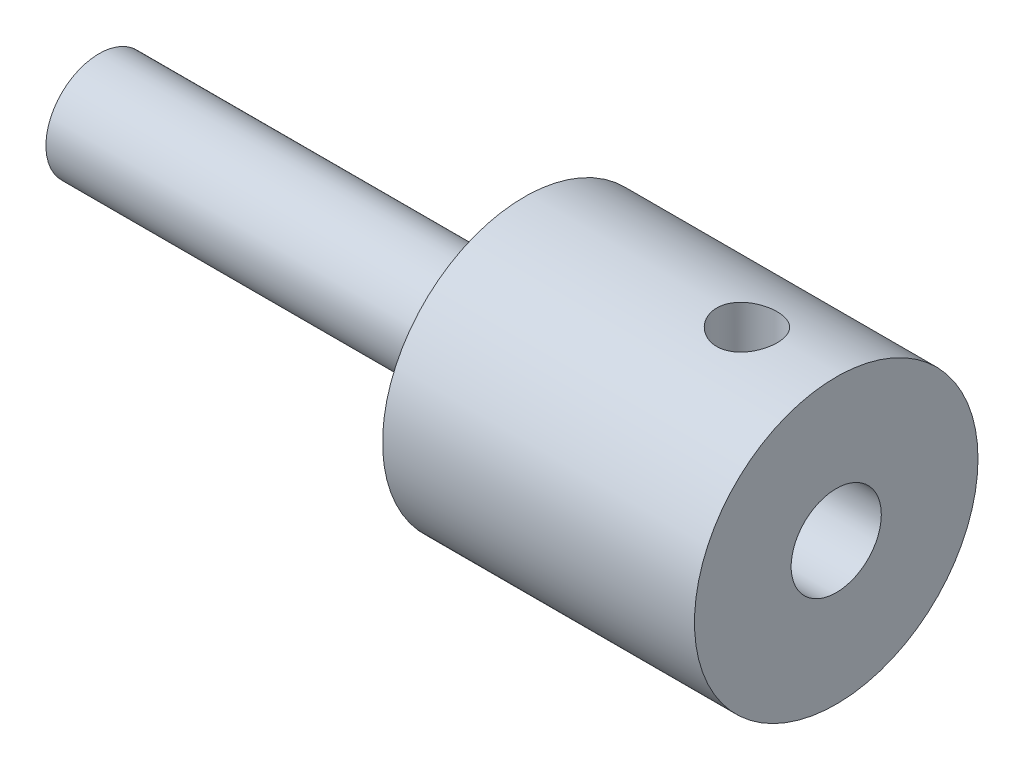
SolidWorks part; units mm, degrees
material "Plain Carbon Steel"
ref_plane "Front Plane" through (0, 0, 0) normal (0, 0, 1) x (1, 0, 0)
ref_plane "Top Plane" through (0, 0, 0) normal (0, 1, 0) x (1, 0, 0)
ref_plane "Right Plane" through (0, 0, 0) normal (1, 0, 0) x (0, 0, -1)
sketch "Sketch1" plane through (0, 0, 0) normal (1, 0, 0) x (0, 0, -1)
  circle A0 centre (0, 0) radius 6.35
  dimension "D1" = 12.7
extrude "Boss-Extrude1" add sketch "Sketch1" along normal blind 33.02
hole_wizard "#21 (0.159) Diameter Hole1" positions "Sketch4" profile "Sketch3" hole size "#21" standard "ANSI Inch"
sketch "Sketch4" plane through (33.02, 0, 0) normal (1, 0, 0) x (0, 0, -1)
  point P0 (0, 0)
sketch "Sketch3" plane through (33.02, 0, 0) normal (0, 1, 0) x (0, 0, -1)
  line L0 (0, 0) -> (0, 9.2133)
  line L1 (0, 9.2133) -> (2.0193, 8)
  line L2 (2.0193, 8) -> (2.0193, 0)
  line L5 (2.0193, 0) -> (0, 0)
  line L10 (0, 9.2133) -> (-2.0193, 8) construction
  line L11 (0, -6.35) -> (0, 107.95) construction
  dimension "Hole Dia." = 4.0386
  dimension "Hole Depth" = 8
  dimension "Drill Angle" = 118
hole_wizard "#6-32 Tapped Hole1" positions "Sketch6" profile "Sketch5" tap size "#6-32" standard "ANSI Inch" end condition up to next
sketch "Sketch6" plane through (0, 0, 0) normal (0, 1, 0) x (1, 0, 0)
  line L0 (33.02, -6.35) -> (33.02, 6.35) construction
  point P0 (29.02, 0)
  dimension "D1" = 4
sketch "Sketch5" plane through (29.02, 0, 0) normal (1, 0, 0) x (0, 0, -1)
  line L0 (0, 0) -> (0, 6.35)
  line L1 (0, 6.35) -> (1.3525, 6.35)
  line L2 (1.3525, 6.35) -> (1.3525, 0)
  line L5 (1.3525, 0) -> (0, 0)
  line L11 (0, -6.35) -> (0, 107.95) construction
  dimension "Thru Tap Drill Dia." = 2.7051
  dimension "Thru Tap Drill Depth" = 6.35
cosmetic thread "Hole Thread1" parameters "D2"=3.5052
sketch "Sketch7" plane through (0, 0, 0) normal (0, 1, 0) x (1, 0, 0)
  line L1 (0, 6.35) -> (19.05, 6.35)
  line L2 (0, 6.35) -> (0, 2.3813)
  line L3 (0, 2.3813) -> (19.05, 2.3813)
  line L4 (19.05, 6.35) -> (19.05, 2.3813)
  dimension "D1" = 19.05
  dimension "D2" = 2.3813
ref_axis "Axis1" through (33.02, 0, 0) along (-1, 0, 0)
revolve "Cut-Revolve1" cut sketch "Sketch7" angle 360 about axis through (33.02, 0, 0) along (-1, 0, 0)
